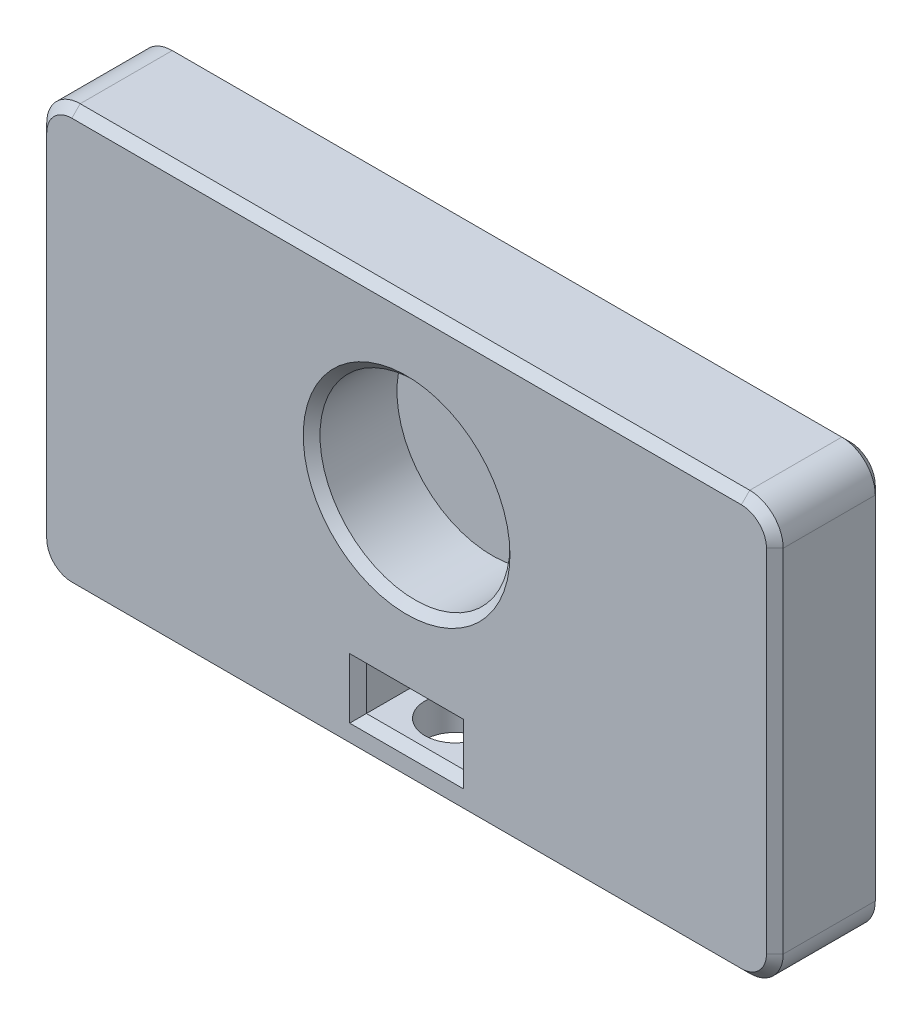
SolidWorks part; units mm, degrees
ref_plane "Front" through (0, 0, 0) normal (0, 0, 1) x (1, 0, 0)
ref_plane "Top" through (0, 0, 0) normal (0, 1, 0) x (1, 0, 0)
ref_plane "Right" through (0, 0, 0) normal (1, 0, 0) x (0, 0, -1)
sketch "Skizze1" plane through (0, 0, 0) normal (0, 0, 1) x (1, 0, 0)
  line L0 (22, 10) -> (-22, 10)
  line L1 (-22, -15) -> (22, -15)
  line L2 (-22, -15) -> (-22, 10)
  line L3 (-22, 15) -> (22, 15) construction
  line L4 (22, -15) -> (22, 10)
  line L5 (-22, -15) -> (22, 15) construction
  line L6 (-22, 15) -> (22, -15) construction
  line L7 (-22, 10) -> (-22, 15) construction
  line L8 (22, 10) -> (22, 15) construction
  point P0 (0, 0)
  dimension "D1" = 44
  dimension "D2" = 30
  dimension "D3" = 5
extrude "Aufsatz-Linear austragen1" add sketch "Skizze1" along normal blind 6.5
sketch "Skizze2" plane through (0, 0, 6.5) normal (0, 0, 1) x (1, 0, 0)
  circle A0 centre (0, 0) radius 5.675
  dimension "D1" = 11.35
extrude "Schnitt-Linear austragen1" cut sketch "Skizze2" against normal blind 5.1
fillet "Verrundung1" radius 2 4 edges at (22, 10, 3.25) (22, -15, 3.25) (-22, 10, 3.25) (-22, -15, 3.25)
sketch "Skizze8" plane through (0, 0, 6.5) normal (0, 0, 1) x (1, 0, 0)
  line L0 (0, 0) -> (0, -19.4862) construction
  line L1 (-2.9, -13) -> (2.9, -13)
  line L2 (2.9, -13) -> (2.9, -10.4)
  line L3 (2.9, -10.4) -> (-2.9, -10.4)
  line L4 (-20, -15) -> (20, -15) construction
  line L5 (-2.9, -13) -> (-2.9, -10.4)
  point P10 (0, -10.4)
  point P11 (0, -13)
  dimension "D1" = 2.6
  dimension "D2" = 2
  dimension "D3" = 5.8
extrude "Schnitt-Linear austragen5" cut sketch "Skizze8" against normal offset from surface (4.5 mm away) 2 up to face at (0, -2.5, 0)
sketch "Skizze9" plane through (0, -10.4, 0) normal (0, -1, 0) x (1, 0, 0)
  line L0 (-2.775, 2) -> (0, 0.3979)
  line L1 (0, 0) -> (0, 8.8539) construction
  line L2 (-20, 0) -> (20, 0) construction
  line L3 (2.775, 2) -> (0, 0.3979)
  line L4 (-2.775, 2) -> (2.775, 2)
  line L5 (2.775, 2) -> (2.775, 5.2043) construction
  line L6 (2.775, 5.2043) -> (0, 6.8064) construction
  line L7 (-2.775, 5.2043) -> (0, 6.8064) construction
  line L8 (-2.775, 2) -> (-2.775, 5.2043) construction
  line L9 (-2.775, 5.2043) -> (2.775, 2) construction
  circle A0 centre (0, 3.6021) radius 1.8
  line M6 (-2.9, 2) -> (2.9, 2)
  dimension "D4" = 3.6
  dimension "D1" = 5.55
  dimension "D2" = 2
  dimension "D3" = 120
extrude "Schnitt-Linear austragen6" cut sketch "Skizze9" along normal up to surface (2.6 mm away) contours A0 L0 L3 M6 | L4 A0 region at (0, -10.4, 1.4424) region at (0, -10.4, 1.9205) up to face at (0, -13, 4.25)
extrude "Schnitt-Linear austragen7" cut sketch "Skizze9<3>" along normal through all and the other way blind 4.1 contours L4 A0 | L4 A0 region at (0, -10.4, 3.6391) region at (0, -10.4, 1.9205)
sketch "Skizze9<3>" plane through (0, -10.4, 0) normal (0, -1, 0) x (1, 0, 0) same geometry as "Skizze9"
chamfer "Fase1" distance 0.5 angle 45 21 edges at (21.4142, -14.4142, 6.5) (0, -15, 6.5) (-21.4142, -14.4142, 6.5) (-22, -2.5, 6.5) (-21.4142, 9.4142, 6.5) (0, 10, 6.5) (21.4142, 9.4142, 6.5) (22, -2.5, 6.5) (5.675, 0, 6.5) (0, -10.4, 6.5) (-2.9, -11.7, 6.5) (0, -13, 6.5) (2.9, -11.7, 6.5) (-21.4142, 9.4142, 0) (-22, -2.5, 0) (-21.4142, -14.4142, 0) (0, -15, 0) (21.4142, -14.4142, 0) (22, -2.5, 0) (21.4142, 9.4142, 0) (0, 10, 0)
